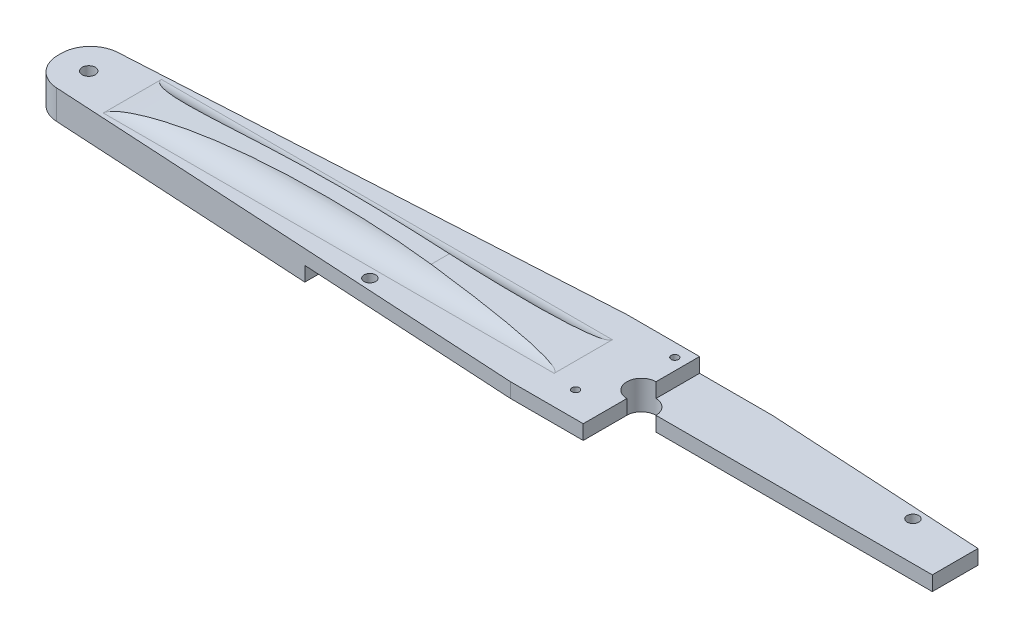
SolidWorks part; units mm, degrees
material "Polylactic Acid (PLA)"
ref_plane "Front Plane" through (0, 0, 0) normal (0, 0, 1) x (1, 0, 0)
ref_plane "Top Plane" through (0, 0, 0) normal (0, 1, 0) x (1, 0, 0)
ref_plane "Right Plane" through (0, 0, 0) normal (1, 0, 0) x (0, 0, -1)
sketch "Sketch2" plane through (0, 0, 0) normal (0, 0, 1) x (1, 0, 0)
  line L0 (0, 0) -> (200, 0)
  line L1 (55, 0) -> (-55, 0) construction
  line L2 (200, 0) -> (200, 10)
  line L3 (200, 10) -> (-200, 10)
  line L4 (-200, 10) -> (-200, 0)
  line L5 (-200, 0) -> (0, 0)
  line L6 (0, -55) -> (0, 55) construction
  dimension "D1" = 10
  dimension "D2" = 200
  dimension "D3" = 200
extrude "Boss-Extrude1" add sketch "Sketch2" along normal mid plane 40
sketch "Sketch3" plane through (0, 10, 0) normal (0, 1, 0) x (1, 0, 0)
  line L1 (0, 0) -> (-5.567, 9.6423) construction
  line L2 (0, 0) -> (16, 0) construction
  line L3 (-200, -20) -> (-200, 20) construction
  line L4 (0, -55) -> (0, 55) construction
  circle A0 centre (-4, 15.4919) radius 1.25
  circle A1 centre (15.4164, -4.2819) radius 1.25
  circle A2 centre (-11.4164, -11.2101) radius 1.25
  circle A3 centre (0, 0) radius 5
  circle A4 centre (-190, 0) radius 2.25
  circle A5 centre (190, 0) radius 2.25
  point P10 (0, 0)
  dimension "D1" = 3
  dimension "D3" = 10
  dimension "D4" = 16
  dimension "D2" = 120
  dimension "D5" = 4
extrude "Cut-Extrude1" cut sketch "Sketch3" against normal blind 40
sketch "Sketch4" plane through (0, 10, 0) normal (0, 1, 0) x (1, 0, 0)
  line L0 (-55, 0) -> (55, 0) construction
  line L1 (-205.6824, 30.2666) -> (-25, 30.2666)
  line L2 (-205.6824, 30.2666) -> (-205.6824, 10)
  line L3 (-205.6824, 10) -> (-200, 10)
  line L4 (-25, 30.2666) -> (-25, 20)
  line L5 (-200, -20) -> (-200, 20) construction
  line L6 (-25, 20) -> (-200, 10)
  line L7 (200, 20) -> (-200, 20) construction
  dimension "D1" = 10
  dimension "D2" = 175
extrude "Cut-Extrude2" cut sketch "Sketch4" against normal blind 40
mirror "Mirror1" about plane through (0, 0, 0) normal (1, 0, 0) of "Cut-Extrude2"
mirror "Mirror2" about plane through (0, 0, 0) normal (0, 0, 1) of "Mirror1", "Cut-Extrude2"
sketch "Sketch5" plane through (0, 0, 0) normal (0, 0, 1) x (1, 0, 0)
  line L1 (-175, 10) -> (-20, 10)
  line L2 (-130, 20) -> (-20, 10)
  line L5 (-200, 10) -> (-25, 10) construction
  line L6 (-175, 10) -> (-130, 20)
extrude "Boss-Extrude3" add sketch "Sketch5" along normal mid plane 5
mirror "Mirror3" about plane through (0, 0, 0) normal (1, 0, 0) of "Boss-Extrude3"
sketch "Sketch6" plane through (0, 0, 0) normal (0, 0, 1) x (1, 0, 0)
  line L1 (207.3185, 0) -> (100, 0)
  line L2 (207.3185, 0) -> (207.3185, 36.5937)
  line L3 (207.3185, 36.5937) -> (100, 36.5937)
  line L4 (100, 0) -> (100, 36.5937)
extrude "Cut-Extrude3" cut sketch "Sketch6" against normal mid plane 50
sketch "Sketch7" plane through (0, 0, 0) normal (0, 0, 1) x (1, 0, 0)
  line L0 (0, -8.8605) -> (0, 8.8605) construction
  line L1 (0, 5) -> (103.8503, 5)
  line L2 (0, 5) -> (0, 20.7181)
  line L3 (0, 20.7181) -> (103.8503, 20.7181)
  line L4 (103.8503, 5) -> (103.8503, 20.7181)
  line L5 (22, 0) -> (-22, 0) construction
  dimension "D1" = 5
extrude "Cut-Extrude4" cut sketch "Sketch7" against normal blind 50
sketch "Sketch8" plane through (0, 0, 0) normal (0, 0, 1) x (1, 0, 0)
  line L0 (0, -11) -> (0, 11) construction
  line L1 (0, 23.5549) -> (102.4935, 23.5549)
  line L2 (0, 23.5549) -> (0, 0)
  line L3 (0, 0) -> (102.4935, 0)
  line L4 (102.4935, 23.5549) -> (102.4935, 0)
  line L5 (22, 0) -> (-22, 0) construction
extrude "Cut-Extrude5" cut sketch "Sketch8" along normal blind 50
sketch "Sketch9" plane through (0, 0, 0) normal (0, 0, 1) x (1, 0, 0)
  line L0 (22, 0) -> (-22, 0) construction
  line L1 (0, 0) -> (-100, 0)
  line L2 (0, 0) -> (0, 5)
  line L3 (0, 5) -> (-100, 5)
  line L4 (-100, 0) -> (-100, 5)
  dimension "D1" = 5
extrude "Cut-Extrude6" cut sketch "Sketch9" along normal blind 50
fillet "Fillet1" radius 400 1 edges at (-130, 20, 0)
fillet "Fillet2" radius 10 2 edges at (-200, 5, -10) (-200, 5, 10)
fillet "Fillet3" radius 7.5 2 edges at (-97.5, 10, 2.5) (-97.5, 10, -2.5)
sketch "Sketch10" plane through (0, 0, 0) normal (0, -1, 0) x (1, 0, 0)
  line L0 (-100, 15.7143) -> (-25, 20) construction
  line L2 (0, -20) -> (0, -5) construction
  line L3 (100, -15.7143) -> (25, -20) construction
  line L4 (0, 5) -> (0, 20) construction
  circle A0 centre (-80, 13.3514) radius 2
  circle A1 centre (80, -13.3514) radius 2
  dimension "D1" = 3.5
  dimension "D5" = 4
  dimension "D6" = 4
  dimension "D2" = 3.5
  dimension "D3" = 80
  dimension "D4" = 80
extrude "Cut-Extrude7" cut sketch "Sketch10" against normal blind 10
